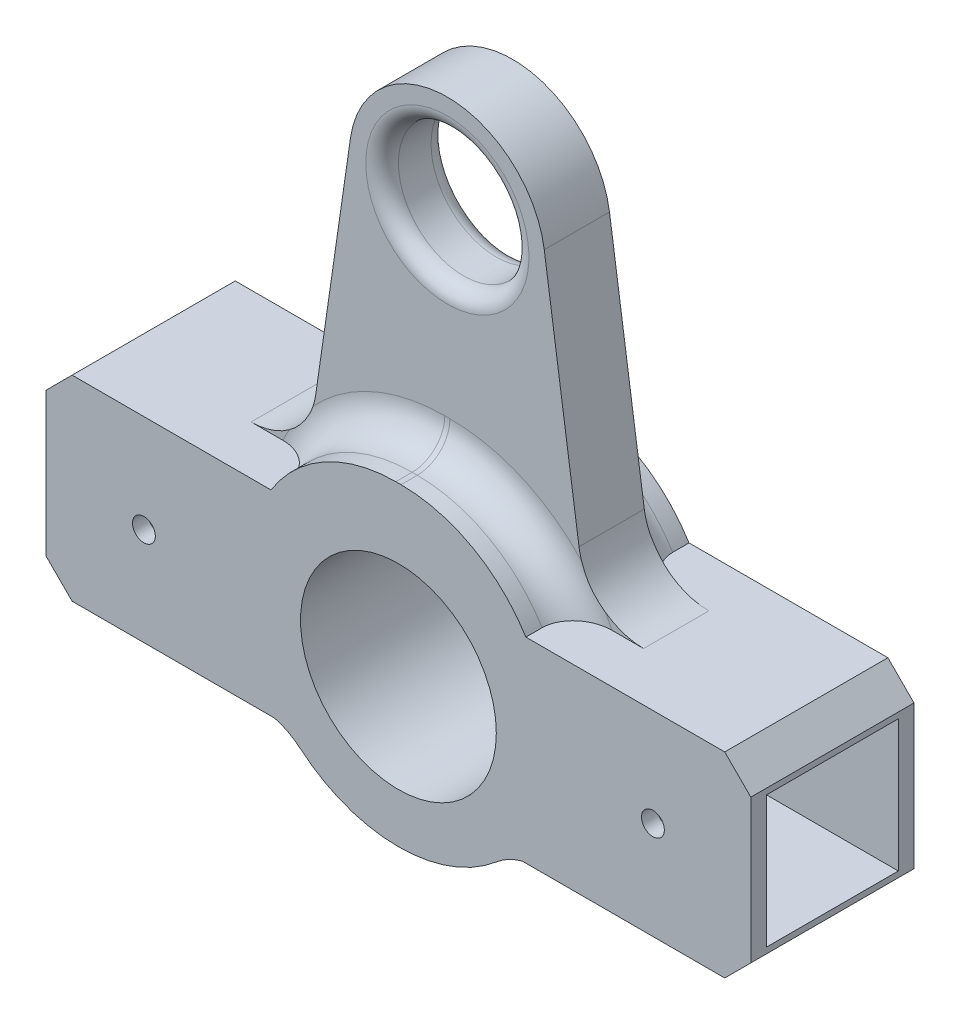
SolidWorks part; units mm, degrees
ref_plane "Alzado" through (0, 0, 0) normal (0, 0, 1) x (1, 0, 0)
ref_plane "Planta" through (0, 0, 0) normal (0, 1, 0) x (1, 0, 0)
ref_plane "Vista lateral" through (0, 0, 0) normal (1, 0, 0) x (0, 0, -1)
sketch "Croquis1" plane through (0, 0, 0) normal (0, 0, 1) x (1, 0, 0)
  line L0 (0, -17.338) -> (0, 18.662) construction
  line L1 (18, 0.662) -> (-18, 0.662) construction
  line L2 (0, 0.662) -> (0, 58.162) construction
  line L3 (-23.0094, 3.9979) -> (-14.8448, 60.3142)
  line L5 (23.0094, 3.9979) -> (14.8448, 60.3142)
  circle A0 centre (0, 0) radius 15
  arc A6 (14.8448, 60.3142) -> (-14.8448, 60.3142) centre (0, 58.162) ccw
  arc A7 (-23.0094, 3.9979) -> (23.0094, 3.9979) centre (0, 0.662) ccw
  circle A8 centre (0, 58.162) radius 10
  point P7 (0, 0.662)
  point P11 (0, 0.662)
  dimension "D1" = 46.5
  dimension "D2" = 30
  dimension "D6" = 30
  dimension "D7" = 20
  dimension "D3" = 18
  dimension "D5" = 57.5
extrude "Saliente-Extruir1" add sketch "Croquis1" along normal mid plane 25
sketch "Croquis3" plane through (0, 0, 0) normal (1, 0, 0) x (0, 0, -1)
  line L1 (12.5, 73.162) -> (-12.5, 73.162) construction
  line L2 (5, 73.162) -> (5, 25.662)
  line L4 (-5, 25.662) -> (-5, 73.162)
  line L6 (-5, 73.162) -> (-12.5, 73.162)
  line L7 (-12.5, 73.162) -> (-12.5, 25.662)
  line L8 (-12.5, 3.9979) -> (-12.5, 60.3142) construction
  line L9 (-12.5, 25.662) -> (-5, 25.662)
  line L10 (5, 25.662) -> (12.5, 25.662)
  line L11 (12.5, 3.9979) -> (12.5, 60.3142) construction
  line L12 (12.5, 25.662) -> (12.5, 73.162)
  line L13 (12.5, 73.162) -> (5, 73.162)
  dimension "D2" = 47.5
  dimension "D3" = 7.5
  dimension "D4" = 7.5
extrude "Cortar-Extruir2" cut sketch "Croquis3" against normal through all both and the other way through all
fillet "Redondeo3" radius 22.5 4 edges at (-19.8686, 25.662, 8.75) (19.8686, 25.662, 8.75) (-19.8686, 25.662, -8.75) (19.8686, 25.662, -8.75)
sketch "Croquis4" plane through (0, 0, -12.5) normal (0, 0, -1) x (-1, 0, 0)
  line L0 (0, 0) -> (-19, 0) construction
  line L1 (-19, 15) -> (-19, -15)
  line L2 (-19, 15) -> (-54, 15)
  line L3 (-54, 15) -> (-54, -15)
  line L4 (-54, -15) -> (-19, -15)
  line L5 (0, 0) -> (0, 9.1483) construction
  line L6 (54, 15) -> (54, -15)
  line L7 (19, 15) -> (54, 15)
  line L8 (19, 15) -> (19, -15)
  line L9 (54, -15) -> (19, -15)
  line L10 (-54, 0) -> (-39, 0) construction
  circle A0 centre (-39, 0) radius 1.75
  circle A1 centre (39, 0) radius 1.75
  point P6 (-19, 0)
  dimension "D4" = 3.5
  dimension "D1" = 30
  dimension "D2" = 19
  dimension "D3" = 35
  dimension "D5" = 15
extrude "Saliente-Extruir2" add sketch "Croquis4" against normal blind 25
sketch "Croquis5" plane through (54, 0, 0) normal (1, 0, 0) x (0, 0, -1)
  line L1 (-10.1, 10.1) -> (10.1, 10.1)
  line L2 (-10.1, 10.1) -> (-10.1, -10.1)
  line L3 (-10.1, -10.1) -> (10.1, -10.1)
  line L4 (10.1, 10.1) -> (10.1, -10.1)
  line L5 (-10.1, 10.1) -> (10.1, -10.1) construction
  line L6 (-10.1, -10.1) -> (10.1, 10.1) construction
  point P0 (0, 0)
  dimension "D1" = 20.2
  dimension "D2" = 20.2
extrude "Cortar-Extruir3" cut sketch "Croquis5" against normal blind 30
mirror "Simetría1" about plane through (0, 0, 0) normal (1, 0, 0) of "Cortar-Extruir3"
fillet "Redondeo4" radius 10 4 edges at (-19, -12.7381, 0) (19, -12.7381, 0) (21.4144, 15, 0) (-21.4144, 15, 0)
chamfer "Chaflán1" distance 4 angle 45 4 edges at (54, 15, 0) (54, -15, 0) (-54, -15, 0) (-54, 15, 0)
fillet "Redondeo5" radius 5 6 edges at (11.3475, 22.8166, -5) (0, 25.662, -5) (-11.3475, 22.8166, 5) (0, 25.662, 5) (-11.3475, 22.8166, -5) (11.3475, 22.8166, 5)
fillet "Redondeo6" radius 2.5 2 edges at (-10, 58.162, 5) (0, 48.162, -5)
